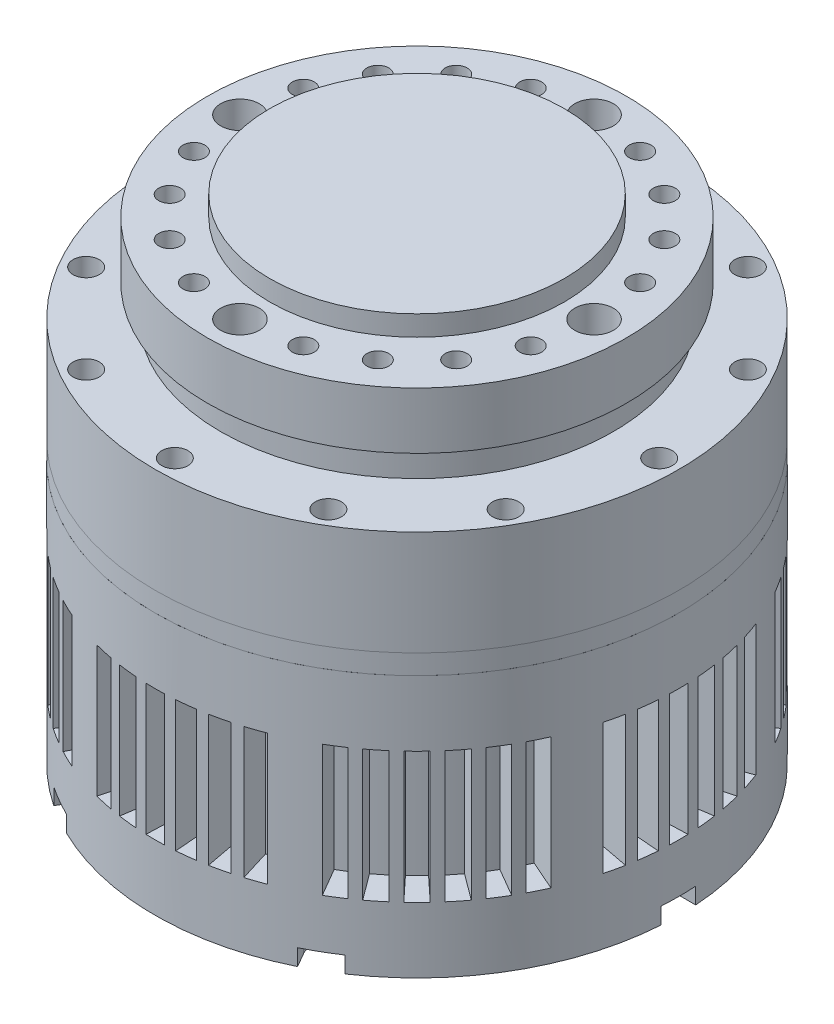
SolidWorks part; units mm, degrees
ref_plane "Front Plane" through (0, 0, 0) normal (0, 0, 1) x (1, 0, 0)
ref_plane "Top Plane" through (0, 0, 0) normal (0, 1, 0) x (1, 0, 0)
ref_plane "Right Plane" through (0, 0, 0) normal (1, 0, 0) x (0, 0, -1)
sketch "Sketch1" plane through (0, 0, 0) normal (0, 1, 0) x (1, 0, 0)
  circle A0 centre (0, 0) radius 40
  dimension "D1" = 80
extrude "Boss-Extrude1" add sketch "Sketch1" along normal blind 16 contours A0
sketch "Sketch2" plane through (0, 16, 0) normal (0, 1, 0) x (1, 0, 0)
  circle A0 centre (0, 37) radius 2
  dimension "D1" = 4
  dimension "D2" = 37
extrude "Cut-Extrude1" cut sketch "Sketch2" against normal blind 5
pattern_circular "CirPattern1" count 12 over 360 about axis through (0, 16, 0) along (0, 1, 0) of "Cut-Extrude1"
sketch "Sketch3" plane through (0, 0, 0) normal (0, -1, 0) x (1, 0, 0)
  circle A0 centre (0, 0) radius 40
  circle A1 centre (0, 0) radius 40 construction
extrude "Boss-Extrude2" add sketch "Sketch3" along normal blind 3 separate body
sketch "Sketch4" plane through (0, -3, 0) normal (0, -1, 0) x (1, 0, 0)
  circle A0 centre (0, 0) radius 40
  circle A1 centre (0, 0) radius 40 construction
extrude "Boss-Extrude3" add sketch "Sketch4" along normal blind 40 separate body
sketch "Sketch5" plane through (0, -43, 0) normal (0, -1, 0) x (1, 0, 0)
  line L0 (-10.2297, 38.6698) -> (-8.951, 33.8361)
  line L1 (-6.5128, 34.3887) -> (-7.4432, 39.3014)
  line L2 (-5.1323, 34.6217) -> (-5.8655, 39.5676)
  line L3 (-2.6478, 34.8997) -> (-3.0261, 39.8854)
  line L4 (-1.4286, 39.9745) -> (-1.25, 34.9777)
  line L5 (1.4286, 39.9745) -> (1.25, 34.9777)
  line L6 (2.6478, 34.8997) -> (3.0261, 39.8854)
  line L7 (5.1323, 34.6217) -> (5.8655, 39.5676)
  line L8 (7.4432, 39.3014) -> (6.5128, 34.3887)
  line L9 (10.2297, 38.6698) -> (8.951, 33.8361)
  line L10 (14.4669, 37.2922) -> (12.6585, 32.6307)
  line L11 (11.768, 38.2298) -> (10.297, 33.451)
  line L12 (-6.978, 36.845) -> (-5.4989, 37.0946) construction
  line L13 (-2.837, 37.3925) -> (-1.3393, 37.4761) construction
  line L14 (1.3393, 37.4761) -> (2.837, 37.3925) construction
  line L15 (5.4989, 37.0946) -> (6.978, 36.845) construction
  line L16 (9.5903, 36.2529) -> (11.0325, 35.8404) construction
  line L17 (-9.5903, 36.2529) -> (-6.978, 36.845) construction
  line L18 (-5.4989, 37.0946) -> (-2.837, 37.3925) construction
  line L19 (-1.3393, 37.4761) -> (1.3393, 37.4761) construction
  line L20 (2.837, 37.3925) -> (5.4989, 37.0946) construction
  line L21 (6.978, 36.845) -> (9.5903, 36.2529) construction
  line L22 (11.0325, 35.8404) -> (13.5627, 34.9614) construction
  line L23 (28.7562, 44.6999) -> (-40.4872, 34.4353) construction
  line L24 (-5.8655, 39.5676) -> (0, 0) construction
  arc A0 (12.6585, 32.6307) -> (10.297, 33.451) centre (0, 0) ccw
  circle A1 centre (0, 0) radius 40 construction
  arc A3 (14.4669, 37.2922) -> (11.768, 38.2298) centre (0, 0) ccw
  arc A5 (-3.0261, 39.8854) -> (-5.8655, 39.5676) centre (0, 0) ccw
  arc A6 (1.4286, 39.9745) -> (-1.4286, 39.9745) centre (0, 0) ccw
  arc A7 (5.8655, 39.5676) -> (3.0261, 39.8854) centre (0, 0) ccw
  arc A8 (10.2297, 38.6698) -> (7.4432, 39.3014) centre (0, 0) ccw
  arc A9 (8.951, 33.8361) -> (6.5128, 34.3887) centre (0, 0) ccw
  arc A10 (5.1323, 34.6217) -> (2.6478, 34.8997) centre (0, 0) ccw
  arc A11 (1.25, 34.9777) -> (-1.25, 34.9777) centre (0, 0) ccw
  arc A12 (-2.6478, 34.8997) -> (-5.1323, 34.6217) centre (0, 0) ccw
  arc A13 (-6.5128, 34.3887) -> (-8.951, 33.8361) centre (0, 0) ccw
  arc A14 (-7.4432, 39.3014) -> (-5.8655, 39.5676) centre (0, 0) cw construction
  arc A15 (-1.4286, 39.9745) -> (-3.0261, 39.8854) centre (0, 0) ccw construction
  arc A16 (3.0261, 39.8854) -> (1.4286, 39.9745) centre (0, 0) ccw construction
  arc A17 (7.4432, 39.3014) -> (5.8655, 39.5676) centre (0, 0) ccw construction
  arc A18 (11.768, 38.2298) -> (10.2297, 38.6698) centre (0, 0) ccw construction
  arc A19 (-7.4432, 39.3014) -> (-10.2297, 38.6698) centre (0, 0) ccw
  point P15 (-5.8655, 39.5676)
  point P42 (-4.1679, 37.2436)
  point P46 (-9.9532, 38.7419)
  point P47 (-7.5295, 34.1805)
  point P50 (0, 35)
  dimension "D1" = 5
  dimension "D2" = 2.5
  dimension "D3" = 70
  dimension "D4" = 1.5
sketch "Sketch6" plane through (0, 16, 0) normal (0, 1, 0) x (1, 0, 0)
  circle A0 centre (0, 0) radius 40 construction
  circle A1 centre (0, 0) radius 30
  dimension "D1" = 80
  dimension "D2" = 10
extrude "Boss-Extrude4" add sketch "Sketch6" along normal blind 4.75 separate body
sketch "Sketch8" plane through (0, 20.75, 0) normal (0, 1, 0) x (1, 0, 0)
  circle A0 centre (0, 0) radius 32
  dimension "D1" = 64
extrude "Boss-Extrude5" add sketch "Sketch8" along normal blind 8.65 separate body
sketch "Sketch9" plane through (0, 29.4, 0) normal (0, 1, 0) x (1, 0, 0)
  circle A0 centre (0, 0) radius 22.5
  dimension "D1" = 45
extrude "Boss-Extrude6" add sketch "Sketch9" along normal blind 3.1
sketch "Sketch10" plane through (0, 29.4, 0) normal (0, 1, 0) x (1, 0, 0)
  circle A40 centre (0, 27.05) radius 2.95
  point P90 (0, 0)
  dimension "D1" = 27.05
  dimension "D2" = 5.9
extrude "Cut-Extrude5" cut sketch "Sketch10" against normal blind 7
pattern_circular "CirPattern3" count 4 over 360 about axis through (0, 32.5, 0) along (0, 1, 0) of "Cut-Extrude5"
sketch "Sketch14" plane through (0, 29.4, 0) normal (0, 1, 0) x (1, 0, 0)
  line L0 (25.7261, 8.3589) -> (25.7261, 0) construction
  line L1 (25.7261, 0) -> (0, 0) construction
  line L2 (0, 0) -> (25.7261, 8.3589) construction
  circle A0 centre (25.7261, 8.3589) radius 1.675
  circle A1 centre (0, 0) radius 27.05 construction
  point P6 (0, 0)
  dimension "D2" = 3.35
  dimension "D1" = 18
extrude "Cut-Extrude6" cut sketch "Sketch14" against normal blind 7
pattern_circular "CirPattern4" count 20 over 360 about axis through (0, 32.5, 0) along (0, 1, 0) skipping 4, 9, 14, 19 of "Cut-Extrude6"
sketch "Sketch16" plane through (0, -43, 0) normal (0, -1, 0) x (1, 0, 0)
  line L0 (-18.6667, 32.3316) -> (18.6667, 32.3316) construction
  line L1 (-16, 32.3316) -> (16, 32.3316) construction
  line L2 (-18.6667, 32.3316) -> (0, 0) construction
  line L3 (0, 0) -> (18.6667, 32.3316) construction
  line L4 (20.9761, 30.9983) -> (22.2649, 33.2306)
  line L5 (16.3573, 33.6649) -> (17.6461, 35.8973)
  circle A0 centre (-18.6667, 32.3316) radius 2.6667 construction
  circle A1 centre (0, 0) radius 40 construction
  arc A2 (16.3573, 33.6649) -> (20.9761, 30.9983) centre (18.6667, 32.3316) ccw construction
  arc A3 (16.3573, 33.6649) -> (20.9761, 30.9983) centre (18.6667, 32.3316) ccw
  arc A4 (17.6461, 35.8973) -> (22.2649, 33.2306) centre (0, 0) cw
  point P8 (0, 32.3316)
  dimension "D3" = 5.3333
  dimension "D1" = 32
  dimension "D2" = 60
extrude "Cut-Extrude8" cut sketch "Sketch16" against normal blind 2.5
pattern_circular "CirPattern5" count 6 over 360 about axis through (0, -43, 0) along (0, -1, 0) of "Cut-Extrude8"
extrude "Cut-Extrude9" cut sketch "Sketch5" against normal blind 20 from offset 10 offset against normal yes
pattern_circular "CirPattern6" count 8 over 360 about axis through (0, 16, 0) along (0, 1, 0) of "Cut-Extrude9"
equation "\"small black ring h\"= 4.75mm"
equation "\"D1@Boss-Extrude4\"=\"small black ring h\""
equation "\"D1@Boss-Extrude5\"=13.4-\"small black ring h\""
